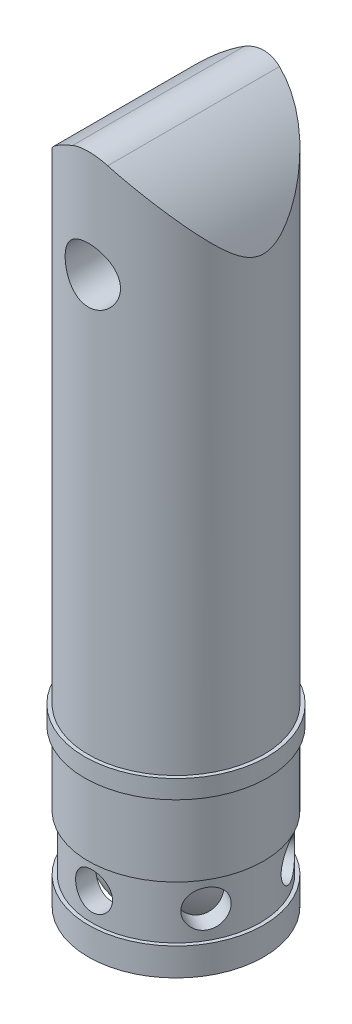
SolidWorks part; units mm, degrees
ref_plane "Front Plane" through (0, 0, 0) normal (0, 0, 1) x (1, 0, 0)
ref_plane "Top Plane" through (0, 0, 0) normal (0, 1, 0) x (1, 0, 0)
ref_plane "Right Plane" through (0, 0, 0) normal (1, 0, 0) x (0, 0, -1)
sketch "Sketch2" plane through (0, 0, 0) normal (0, 1, 0) x (1, 0, 0)
  circle A0 centre (0, 0) radius 4.75
  dimension "D1" = 9.5
extrude "Boss-Extrude2" add sketch "Sketch2" along normal blind 38
sketch "Sketch3" plane through (0, 0, 0) normal (0, 0, 1) x (1, 0, 0)
  line L0 (4.75, 38) -> (4.75, 33)
  line L1 (4.75, 0) -> (4.75, 38) construction
  line L2 (-4.75, 38) -> (-4.75, 33)
  line L3 (-4.75, 38) -> (-4.75, 0) construction
  line L4 (0, 38) -> (0, 21.8398) construction
  line L5 (4.75, 38) -> (-4.75, 38) construction
  line L6 (-4.75, 38) -> (4.75, 38)
  arc A0 (-4.75, 33) -> (0, 38) centre (2.8585, 30.5281) cw
  arc A1 (0, 38) -> (4.75, 33) centre (-2.8585, 30.5281) cw
  dimension "D3" = 8
  dimension "D4" = 8
  dimension "D1" = 5
  dimension "D2" = 5
extrude "Cut-Extrude1" cut sketch "Sketch3" against normal through all both and the other way through all contours L2 A0 L6 | L6 A1 L0 region at (-3.4149, 36.6049, 0) region at (3.4149, 36.6049, 0)
fillet "Fillet1" radius 2 1 edges at (0, 38, 0)
sketch "Sketch4" plane through (0, 0, 0) normal (0, 0, 1) x (1, 0, 0)
  line L0 (-4.75, 0) -> (4.75, 0) construction
  circle A0 centre (0, 3) radius 1
  point P5 (0, 0)
  dimension "D1" = 2
  dimension "D2" = 3
extrude "Cut-Extrude2" cut sketch "Sketch4" against normal through all both and the other way through all
pattern_circular "CirPattern1" count 3 over 360 about axis through (0, 0, 0) along (0, 1, 0) of "Cut-Extrude2"
sketch "Sketch5" plane through (0, 0, 0) normal (0, 0, 1) x (1, 0, 0)
  line L0 (4.75, 0) -> (4.75, 33.0001) construction
  line L1 (4.75, 9.5) -> (4.95, 9.5)
  line L2 (4.75, 9.5) -> (4.75, 8.5)
  line L3 (4.75, 8.5) -> (4.95, 8.5)
  line L4 (4.95, 9.5) -> (4.95, 8.5)
  line L5 (0, 0) -> (0, 37.8034) construction
  line L6 (-4.75, 0) -> (4.75, 0) construction
  arc A0 (0.9528, 37.5619) -> (-0.9528, 37.5619) centre (0, 35.8034) ccw construction
  dimension "D1" = 0.2
  dimension "D2" = 1
  dimension "D3" = 8.5
revolve "Revolve1" add sketch "Sketch5" angle 360 about L5
sketch "Sketch6" plane through (0, 0, 0) normal (0, 0, 1) x (1, 0, 0)
  line L1 (4.75, 4.5) -> (4.55, 4.5)
  line L2 (4.75, 4.5) -> (4.75, 1.5)
  line L3 (4.75, 1.5) -> (4.55, 1.5)
  line L4 (4.55, 4.5) -> (4.55, 1.5)
  line L7 (-4.75, 0) -> (4.75, 0) construction
  line L8 (4.75, 0) -> (4.75, 8.5) construction
  line L9 (0, 0) -> (0, 37.8034) construction
  arc A0 (0.9528, 37.5619) -> (-0.9528, 37.5619) centre (0, 35.8034) ccw construction
  dimension "D1" = 0.2
  dimension "D2" = 3
  dimension "D3" = 1.5
revolve "Cut-Revolve1" cut sketch "Sketch6" angle 360 about L9
sketch "Sketch7" plane through (0, 0, 0) normal (0, 0, 1) x (1, 0, 0)
  line L0 (0, 0) -> (0, 7)
  line L1 (0, 7) -> (3.5, 7)
  line L2 (3.5, 7) -> (3.5, 2)
  line L3 (3.5, 2) -> (4.25, 0)
  line L4 (-4.75, 0) -> (4.75, 0) construction
  line L5 (4.25, 0) -> (0, 0)
  dimension "D1" = 7
  dimension "D2" = 0.5
  dimension "D3" = 2
  dimension "D4" = 3.5
revolve "Cut-Revolve2" cut sketch "Sketch7" angle 360 about L0
sketch "Sketch8" plane through (0, 0, 0) normal (0, 0, 1) x (1, 0, 0)
  line L0 (0, 0) -> (0, 7)
  line L1 (0, 7) -> (3.5, 7)
  line L2 (3.5, 7) -> (3.5, 3.5)
  arc A0 (3.5, 3.5) -> (0, 0) centre (0, 3.5) cw
  dimension "D3" = 3.5
  dimension "D1" = 7
  dimension "D2" = 3.5
revolve "Revolve2" add sketch "Sketch8" angle 360 about L0
sketch "Sketch9" plane through (0, 0, 0) normal (0, 0, 1) x (1, 0, 0)
  circle A0 centre (0, 32) radius 1.5
  point P2 (0, 0)
  dimension "D1" = 3
  dimension "D2" = 32
extrude "Cut-Extrude3" cut sketch "Sketch9" against normal through all both and the other way through all
